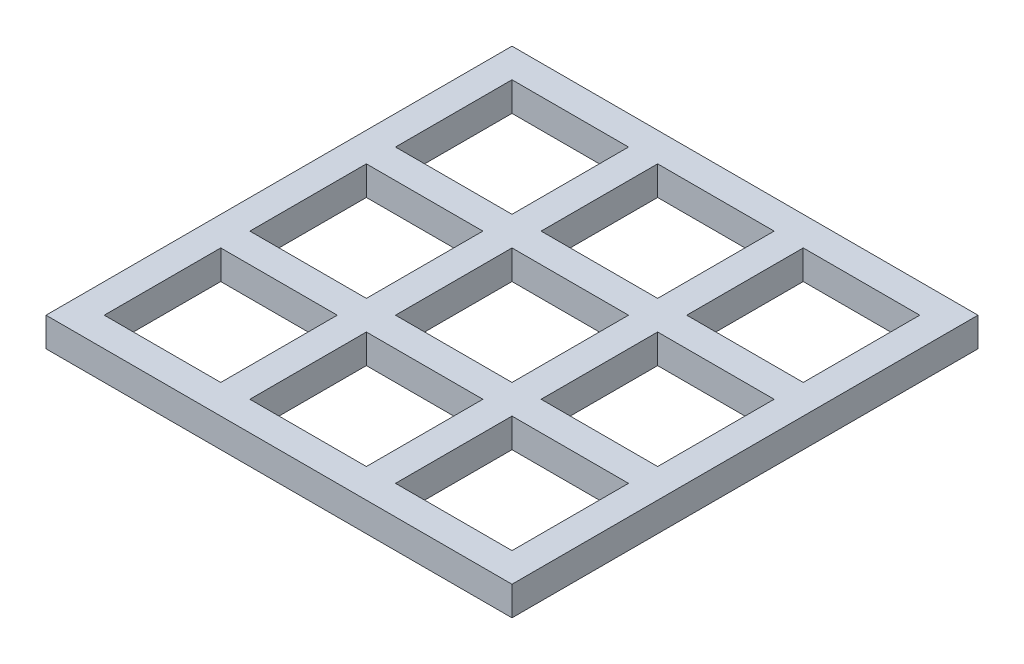
SolidWorks part; units mm, degrees
ref_plane "Front Plane" through (0, 0, 0) normal (0, 0, 1) x (1, 0, 0)
ref_plane "Top Plane" through (0, 0, 0) normal (0, 1, 0) x (1, 0, 0)
ref_plane "Right Plane" through (0, 0, 0) normal (1, 0, 0) x (0, 0, -1)
sketch "Sketch2" plane through (0, 0, 0) normal (0, 1, 0) x (1, 0, 0)
  line L1 (160, -160) -> (-160, -160)
  line L2 (160, -160) -> (160, 160)
  line L3 (160, 160) -> (-160, 160)
  line L4 (-160, -160) -> (-160, 160)
  line L5 (160, -160) -> (-160, 160) construction
  line L6 (160, 160) -> (-160, -160) construction
  point P0 (0, 0)
  dimension "D1" = 320
  dimension "D2" = 320
extrude "Boss-Extrude1" add sketch "Sketch2" along normal blind 20
sketch "Sketch3" plane through (0, 20, 0) normal (0, 1, 0) x (1, 0, 0)
  line L0 (-160, 160) -> (-160, -160) construction
  line L1 (-140, 60) -> (-60, 60)
  line L2 (-140, 60) -> (-140, 140)
  line L3 (-140, 140) -> (-60, 140)
  line L4 (-60, 60) -> (-60, 140)
  line L5 (-140, 60) -> (-60, 140) construction
  line L6 (-140, 140) -> (-60, 60) construction
  line L7 (160, 160) -> (-160, 160) construction
  point P0 (-100, 100)
  dimension "D1" = 80
  dimension "D2" = 80
  dimension "D3" = 20
  dimension "D4" = 20
extrude "Cut-Extrude1" cut sketch "Sketch3" against normal through all
pattern_linear "LPattern1" count 3 spacing 100 along (1, 0, 0) count 3 spacing 100 along (0, 0, 1) of "Cut-Extrude1"
